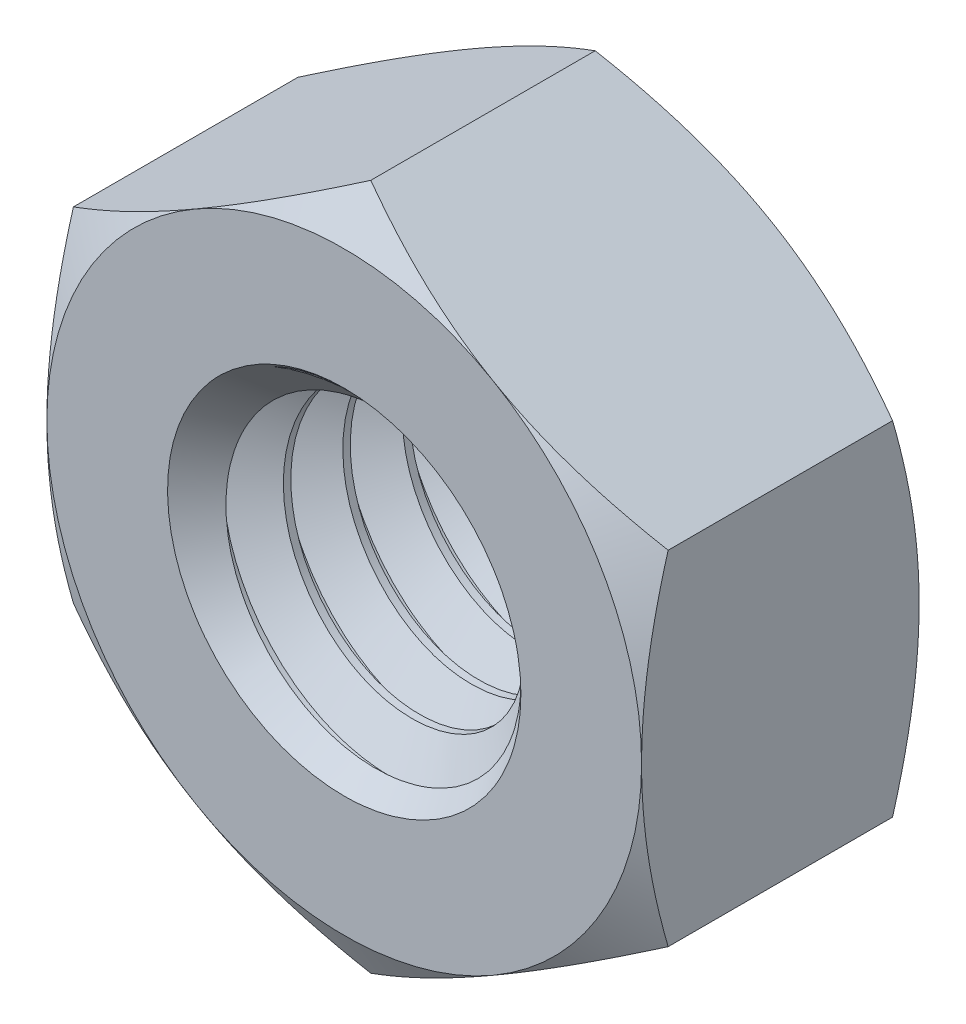
SolidWorks part; units mm, degrees
ref_plane "Front Plane" through (0, 0, 0) normal (0, 0, 1) x (1, 0, 0)
ref_plane "Top Plane" through (0, 0, 0) normal (0, 1, 0) x (1, 0, 0)
ref_plane "Right Plane" through (0, 0, 0) normal (1, 0, 0) x (0, 0, -1)
sketch "Sketch1" plane through (0, 0, 0) normal (1, 0, 0) x (0, 0, -1)
  line L0 (-1.4, 0) -> (1.4, 0) construction
  line L1 (-1.4, -3) -> (-1.4, 3) construction
  line L2 (1.4, -3) -> (1.4, 3) construction
  line L3 (-1.4, -1.75) -> (-1.4, 1.75) construction
  line L4 (-1.9625, 1.815) -> (-1.6625, 1.2953) construction
  line L5 (-1.6625, 1.2953) -> (-1.3625, 1.815) construction
  line L6 (-1.3625, 1.815) -> (-1.9625, 1.815) construction
  line L7 (-1.9438, 1.7825) -> (-1.3813, 1.7825) construction
  line L8 (-1.925, 1.75) -> (-1.4, 1.75) construction
  line L9 (-1.7, 1.3603) -> (-1.625, 1.3603) construction
  line L10 (-1.6625, 1.3603) -> (-1.6625, 1.2953) construction
  line L11 (-1.6625, 1.815) -> (-1.6625, 1.75) construction
  point P4 (0, 0)
  point P7 (-1.4, 0)
  point P11 (1.4, 0)
  point P14 (-1.4, 0)
  point P26 (-1.6625, 1.7825)
  point P27 (-1.4, -1.75)
  dimension "Height" = 2.8
  dimension "Width" = 6
  dimension "Thread OD" = 3.5
  dimension "D1" = 60
  dimension "Pitch" = 0.6
  dimension "D2" = 0.075
sketch "Sketch2" plane through (0, 0, 0) normal (0, 0, 1) x (1, 0, 0)
  line L1 (0, 3.4641) -> (-3, 1.7321)
  line L2 (-3, 1.7321) -> (-3, -1.7321)
  line L3 (-3, -1.7321) -> (0, -3.4641)
  line L4 (0, -3.4641) -> (3, -1.7321)
  line L5 (3, -1.7321) -> (3, 1.7321)
  line L6 (3, 1.7321) -> (0, 3.4641)
  circle A0 centre (0, 0) radius 3 construction
  circle A1 centre (0, 0) radius 1.75
extrude "Boss-Extrude1" add sketch "Sketch2" along normal up to vertex (1.4 mm away) and the other way up to vertex (1.4 mm away) up to point (0, -3, 1.4) other way up to point (0, -3, -1.4)
sketch "Sketch3" plane through (0, 0, 1.4) normal (0, 0, 1) x (1, 0, 0)
  circle A0 centre (0, 0) radius 3
extrude "Cut-Extrude1" cut sketch "Sketch3" against normal through all draft 60 flip side to cut
mirror "Mirror1" about plane through (0, 0, 0) normal (0, 0, 1) of "Cut-Extrude1"
ref_axis "Center Axis 1" through (0, 0, -10.9016) along (0, 0, 1)
ref_plane "Contact Plane 1" through (0, 0, 1.4) normal (0, 0, 1) x (1, 0, 0)
ref_plane "Contact Plane 2" through (0, 0, -1.4) normal (0, 0, -1) x (-1, 0, 0)
sketch "Sketch4" plane through (0, 0, 0) normal (1, 0, 0) x (0, 0, -1)
  line L1 (-1.9438, 1.7825) -> (-1.7, 1.3603)
  line L2 (-1.7, 1.3603) -> (-1.625, 1.3603)
  line L3 (-1.625, 1.3603) -> (-1.3813, 1.7825)
  line L4 (-1.9438, 1.7825) -> (-1.3813, 1.7825) construction
  line L5 (-1.9438, 1.7825) -> (-1.3813, 1.7825)
sketch "Sketch5" plane through (0, 0, 1.4) normal (0, 0, 1) x (1, 0, 0)
  circle A0 centre (0, 0) radius 1.75 construction
  circle A1 centre (0, 0) radius 1.75
curve "Helix/Spiral1" pitch 0.6 height 3.4 radius 1.75 centre (0, 0, 1.4) axis (0, 0, -1) start towards (0, 1, 0)
sweep "Sweep1" add profiles "Sketch4" path "Helix/Spiral1"
sketch "Sketch6" plane through (0, 0, 1.4) normal (0, 0, 1) x (1, 0, 0)
  circle A1 centre (0, 0) radius 1.7825
extrude "Cut-Extrude2" cut sketch "Sketch6" along normal through all and the other way through all draft 45
sketch "Sketch7" plane through (0, 0, -1.4) normal (0, 0, -1) x (-1, 0, 0)
  circle A1 centre (0, 0) radius 1.7825
  circle A2 centre (0, 0) radius 1.7825
  dimension "D1" = 0
extrude "Cut-Extrude3" cut sketch "Sketch7" along normal through all and the other way through all draft 45
equation "\"D2@Sketch1\"=\"Pitch@Sketch1\"/8"
equation "\"D4@Helix/Spiral1\"=\"Pitch@Sketch1\""
equation "\"D3@Helix/Spiral1\"=\"Height@Sketch1\"+\"Pitch@Sketch1\""
